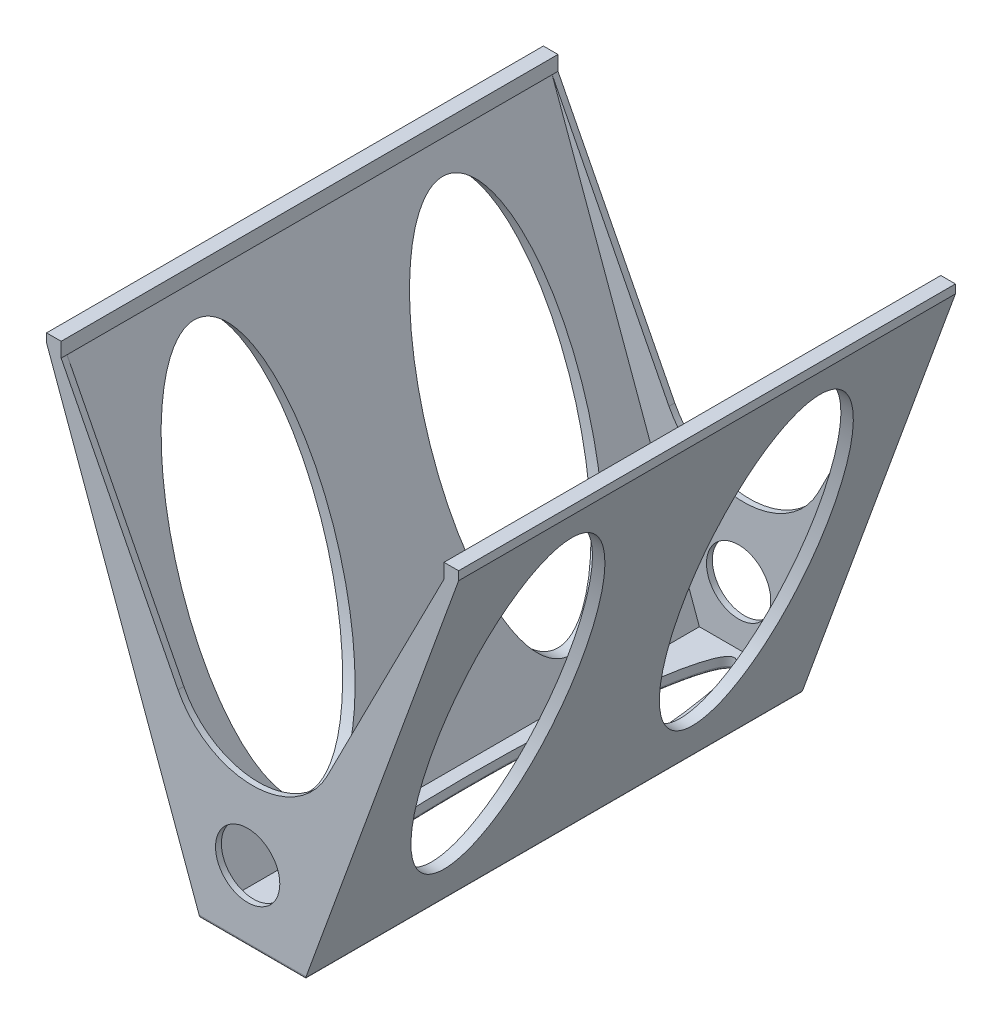
SolidWorks part; units mm, degrees
ref_plane "Front Plane" through (0, 0, 0) normal (0, 0, 1) x (1, 0, 0)
ref_plane "Top Plane" through (0, 0, 0) normal (0, 1, 0) x (1, 0, 0)
ref_plane "Right Plane" through (0, 0, 0) normal (1, 0, 0) x (0, 0, -1)
sketch "Sketch1" plane through (0, 0, 0) normal (0, 0, 1) x (1, 0, 0)
  line L0 (0, 0) -> (0, 145.7232) construction
  line L1 (-70.5, -139) -> (70.5, -139) construction
  line L2 (-70.5, -139) -> (-70.5, 139) construction
  line L3 (-70.5, 139) -> (70.5, 139) construction
  line L4 (70.5, -139) -> (70.5, 139) construction
  line L5 (-70.5, -139) -> (70.5, 139) construction
  line L6 (-70.5, 139) -> (70.5, -139) construction
  line L7 (0, 145.7232) -> (-68, 38.9846) construction
  line L8 (-65.5, 9.4079) -> (-1.6868, 109.5746)
  line L9 (-68.0302, 11.0198) -> (-4.217, 111.1865)
  line L10 (-65.5, 9.4079) -> (-68.0302, 11.0198)
  line L11 (-65.5, 9.4079) -> (-65.5, 8.4079)
  line L12 (-65.5, 8.4079) -> (-70.5, 8.4079)
  line L13 (-70.5, 8.4079) -> (-70.5, 37.3253)
  line L14 (-67.217, 40.2137) -> (-16.8678, 119.246)
  line L15 (-68, 14.5577) -> (-68, 37.5272)
  line L16 (-18.5546, 120.3206) -> (-69.717, 40.0118)
  line L17 (65.5, 9.4079) -> (65.5, 8.4079)
  line L18 (65.5, 9.4079) -> (68.0302, 11.0198)
  line L19 (65.5, 8.4079) -> (70.5, 8.4079)
  line L20 (70.5, 8.4079) -> (70.5, 37.3253)
  line L21 (68, 14.5577) -> (68, 37.5272)
  line L22 (65.5, 9.4079) -> (1.6868, 109.5746)
  line L23 (68.0302, 11.0198) -> (4.217, 111.1865)
  line L24 (67.217, 40.2137) -> (16.8678, 119.246)
  line L25 (18.5546, 120.3206) -> (69.717, 40.0118)
  line L26 (-68.0302, 11.0198) -> (-66.4183, 13.55)
  line L27 (-66.4183, 13.55) -> (-68, 14.5577)
  line L28 (66.4183, 13.55) -> (68, 14.5577)
  line L29 (-65.5, 8.4079) -> (-65.5, 3.4079)
  line L30 (-65.5, 3.4079) -> (-15.1236, -135)
  line L31 (-15.1236, -135) -> (15.1236, -135)
  line L32 (25.5253, -74.8874) -> (65.5, 3.4079)
  line L33 (17.9245, -139) -> (-17.9245, -139)
  line L34 (-17.9245, -139) -> (-70.5, 5.4501)
  line L35 (-70.5, 5.4501) -> (-70.5, 8.4079)
  line L36 (-70.5, 8.4079) -> (-70.5, 5.4501)
  line L37 (65.5, 3.4079) -> (15.1236, -135)
  line L38 (17.9245, -139) -> (70.5, 5.4501)
  line L39 (65.5, 8.4079) -> (70.5, 8.4079)
  line L40 (65.5, 8.4079) -> (65.5, 3.4079)
  line L41 (70.5, 5.4501) -> (70.5, 8.4079)
  line L42 (-25.5253, -74.8874) -> (-65.5, 3.4079)
  arc A0 (-1.6868, 109.5746) -> (1.6868, 109.5746) centre (0, 108.5) cw
  arc A1 (-4.217, 111.1865) -> (4.217, 111.1865) centre (0, 108.5) cw
  arc A2 (-16.8678, 119.246) -> (16.8678, 119.246) centre (0, 108.5) cw
  arc A3 (-69.717, 40.0118) -> (-70.5, 37.3253) centre (-65.5, 37.3253) ccw
  arc A4 (-67.217, 40.2137) -> (-68, 37.5272) centre (-63, 37.5272) ccw
  arc A5 (-18.5546, 120.3206) -> (18.5546, 120.3206) centre (0, 108.5) cw
  arc A6 (67.217, 40.2137) -> (68, 37.5272) centre (63, 37.5272) cw
  arc A7 (69.717, 40.0118) -> (70.5, 37.3253) centre (65.5, 37.3253) cw
  arc A9 (-25.5253, -74.8874) -> (25.5253, -74.8874) centre (0, -61.8551) ccw
  circle A10 centre (-1.6868, -115) radius 11
  point P0 (0, 0)
  point P24 (-70.5, 38.7827)
  dimension "D5" = 2
  dimension "D10" = 5
  dimension "D21" = 22
  dimension "D1" = 141
  dimension "D2" = 278
  dimension "D3" = 32.5
  dimension "D4" = 3
  dimension "D6" = 15
  dimension "D7" = 1
  dimension "D8" = 5
  dimension "D9" = 2
  dimension "D11" = 30.5
  dimension "D12" = 100.1667
  dimension "D13" = 148.4079
  dimension "D14" = 3
  dimension "D15" = 2.5
  dimension "D16" = 5
  dimension "D17" = 4
  dimension "D18" = 4
  dimension "D19" = 70
  dimension "D20" = 20
extrude "Boss-Extrude7" add sketch "Sketch1" along normal blind 2 contours L38 L41 L19 L40 L37 L31 L30 L29 L12 L35 L34 L33 | A9 L42 L30 L31 L37 L32 region at (-67.5399, 5.9079, 0) region at (-47.2099, -36.6063, 0)
extrude "Boss-Extrude8" add sketch "Sketch1<6>" against normal blind 166 contours L38 L41 L19 L40 L37 L31 L30 L29 L12 L35 L34 L33 region at (-67.5399, 5.9079, 0)
sketch "Sketch1<6>" plane through (0, 0, 0) normal (0, 0, 1) x (1, 0, 0) same geometry as "Sketch1"
sketch "Sketch6" plane through (0, 0, -166) normal (0, 0, -1) x (-1, 0, 0)
  line L0 (-17.9245, -139) -> (17.9245, -139)
  line L1 (17.9245, -139) -> (70.5, 5.4501)
  line L2 (17.9245, -139) -> (70.5, 5.4501) construction
  line L3 (70.5, 5.4501) -> (70.5, 8.4079)
  line L4 (70.5, 8.4079) -> (65.5, 8.4079)
  line L5 (65.5, 8.4079) -> (65.5, 3.4079)
  line L6 (65.5, 3.4079) -> (25.5253, -74.8874)
  line L8 (-25.5253, -74.8874) -> (-65.5, 3.4079)
  line L9 (-65.5, 3.4079) -> (-65.5, 8.4079)
  line L10 (-65.5, 8.4079) -> (-70.5, 8.4079)
  line L11 (-70.5, 8.4079) -> (-70.5, 5.4501)
  line L12 (-17.9245, -139) -> (-70.5, 5.4501) construction
  line L13 (-70.5, 5.4501) -> (-70.5, 8.4079) construction
  line L14 (-70.5, 5.4501) -> (-17.9245, -139)
  arc A0 (-25.5253, -74.8874) -> (25.5253, -74.8874) centre (0, -61.8551) ccw
  arc A1 (-25.5253, -74.8874) -> (25.5253, -74.8874) centre (0, -61.8551) ccw construction
  circle A2 centre (1.6868, -115) radius 11
  circle A3 centre (1.6868, -115) radius 11 construction
  point P32 (1.6868, -115)
extrude "Boss-Extrude9" add sketch "Sketch6" along normal blind 2
sketch "Sketch7" plane through (0, -139, 0) normal (0, -1, 0) x (1, 0, 0)
  line L0 (0, 2) -> (0, -168) construction
  line L1 (17.9245, -168) -> (-17.9245, -168) construction
  line L3 (17.9245, 2) -> (-17.9245, 2) construction
  ellipse E0 centre (0, -83) end of major axis (0, -162.8592) minor radius 10.5926
  point P6 (0, 0)
  point P12 (0, 0)
  point P13 (0, 0)
  point P15 (0, 8.4553)
  point P17 (0, 0)
  point P18 (0, -83)
  point P19 (0, -3.1408)
  point P20 (-10.5926, -83)
extrude "Cut-Extrude3" cut sketch "Sketch7" against normal through all
fillet "Fillet1" radius 1 5 edges at (0, -139, 2) (17.9245, -139, -83) (0, -139, -168) (-17.9245, -139, -83) (0, -139, -162.8592)
sketch "Sketch8" plane through (-70.5, 0, 0) normal (-1, 0, 0) x (0, 0, 1)
  line L0 (-83, -138.342) -> (-83, 8.4079) construction
  line L1 (-167.9397, -138.342) -> (1.9397, -138.342) construction
  line L2 (2, 8.4079) -> (-168, 8.4079) construction
  line L3 (-83, -64.9671) -> (-168, -64.9671) construction
  line L4 (-168, -138) -> (-168, 5.4501) construction
  line L5 (-125.5, -4.9671) -> (-125.5, -124.9671) construction
  ellipse E0 centre (-125.5, -64.9671) end of major axis (-125.5, -4.9671) minor radius 25
  ellipse E1 centre (-40.5, -64.9671) end of major axis (-40.5, -4.9671) minor radius 25
  dimension "D1" = 120
  dimension "D2" = 50
  dimension "D3" = 42.5
extrude "Cut-Extrude4" cut sketch "Sketch8" against normal through all
